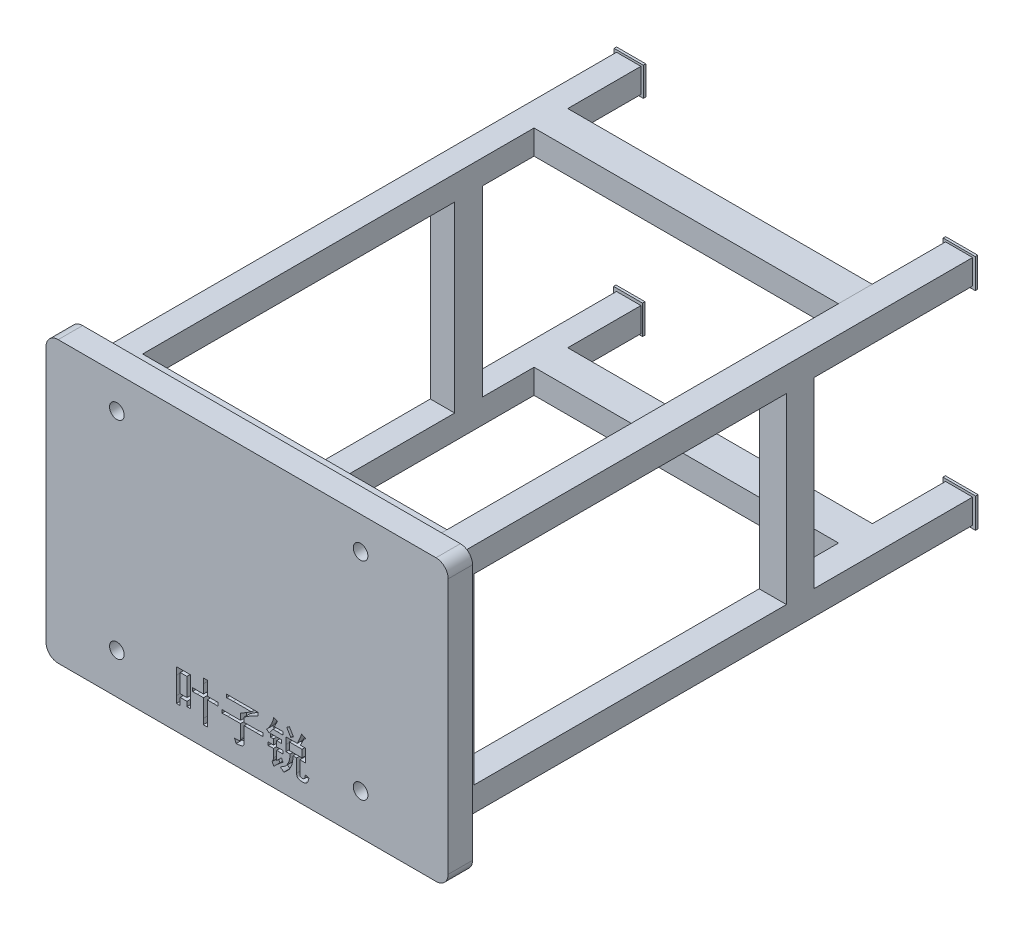
SolidWorks part; units mm, degrees
ref_plane "前视基准面" through (0, 0, 0) normal (0, 0, 1) x (1, 0, 0)
ref_plane "上视基准面" through (0, 0, 0) normal (0, 1, 0) x (1, 0, 0)
ref_plane "右视基准面" through (0, 0, 0) normal (1, 0, 0) x (0, 0, -1)
other "Configuration Table"
sketch "草图1" plane through (0, 0, 0) normal (0, 0, 1) x (1, 0, 0)
  line L0 (-38.1382, 236.709) -> (-38.1382, 26.709)
  line L1 (-28.1382, 16.709) -> (281.8618, 16.709)
  line L2 (291.8618, 26.709) -> (291.8618, 236.709)
  line L3 (281.8618, 246.709) -> (-28.1382, 246.709)
  arc A0 (281.8618, 16.709) -> (291.8618, 26.709) centre (281.8618, 26.709) ccw
  arc A1 (291.8618, 236.709) -> (281.8618, 246.709) centre (281.8618, 236.709) ccw
  arc A2 (-38.1382, 26.709) -> (-28.1382, 16.709) centre (-28.1382, 26.709) ccw
  arc A3 (-38.1382, 236.709) -> (-28.1382, 246.709) centre (-28.1382, 236.709) cw
  dimension "D1" = 10
extrude "凸台-拉伸1" add sketch "草图1" along normal blind 20
sketch "草图2" plane through (0, 0, 20) normal (0, 0, 1) x (1, 0, 0)
  circle A0 centre (20, 220) radius 6
  circle A1 centre (20, 50) radius 6
  circle A2 centre (220, 50) radius 6
  circle A3 centre (220, 220) radius 6
sketch "草图3" plane through (0, 0, 0) normal (0, 0, -1) x (-1, 0, 0)
  line L1 (-250, 230) -> (0, 230)
  line L2 (-250, 230) -> (-250, 210)
  line L3 (-250, 210) -> (0, 210)
  line L4 (0, 230) -> (0, 210)
extrude "凸台-拉伸2" add sketch "草图3" along normal blind 20
sketch "草图4" plane through (0, 0, 0) normal (0, 0, -1) x (-1, 0, 0)
  line L4 (-250, 60) -> (0, 60)
  line L5 (-250, 60) -> (-250, 40)
  line L6 (-250, 40) -> (0, 40)
  line L7 (0, 60) -> (0, 40)
extrude "凸台-拉伸3" add sketch "草图4" along normal blind 20
extrude "切除-拉伸2" cut sketch "草图2<3>" against normal blind 40
sketch "草图2<3>" plane through (0, 0, 20) normal (0, 0, 1) x (1, 0, 0) same geometry as "草图2"
sketch "草图5" plane through (0, 0, 0) normal (0, 0, -1) x (-1, 0, 0)
  line L1 (-272.2176, 230.2498) -> (-250, 230.2498)
  line L2 (-272.2176, 230.2498) -> (-272.2176, 210)
  line L3 (-272.2176, 210) -> (-250, 210)
  line L4 (-250, 230.2498) -> (-250, 210)
  line L8 (-250, 60) -> (-272.2176, 60)
  line L9 (-250, 60) -> (-250, 40)
  line L10 (-250, 40) -> (-272.2176, 40)
  line L11 (-272.2176, 60) -> (-272.2176, 40)
  line L12 (0, 230) -> (20, 230)
  line L13 (0, 230) -> (0, 210)
  line L14 (0, 210) -> (20, 210)
  line L15 (20, 230) -> (20, 210)
  line L17 (0, 60) -> (20, 60)
  line L18 (0, 60) -> (0, 40)
  line L19 (0, 40) -> (20, 40)
  line L20 (20, 60) -> (20, 40)
extrude "凸台-拉伸4" add sketch "草图5" along normal blind 430
sketch "草图6" plane through (0, 0, 0) normal (0, 0, -1) x (-1, 0, 0)
  line L0 (-272.2176, 210) -> (20, 210) construction
  line L1 (-272.2176, 210) -> (-250, 210)
  line L2 (-272.2176, 210) -> (-272.2176, 60)
  line L3 (-272.2176, 60) -> (-250, 60)
  line L4 (-250, 210) -> (-250, 60)
  line L5 (0, 210) -> (20, 210)
  line L6 (0, 210) -> (0, 60)
  line L7 (0, 60) -> (20, 60)
  line L8 (20, 210) -> (20, 60)
extrude "凸台-拉伸6" add sketch "草图6" along normal blind 20
extrude "凸台-拉伸13" add sketch "草图6<5>" along normal blind 300
sketch "草图6<5>" plane through (0, 0, 0) normal (0, 0, -1) x (-1, 0, 0) same geometry as "草图6"
sketch "草图10" plane through (272.2176, 0, 0) normal (1, 0, 0) x (0, 0, -1)
  line L3 (277.2157, 210) -> (20.8428, 210)
  line L4 (277.2157, 210) -> (277.2157, 60)
  line L5 (277.2157, 60) -> (20.8428, 60)
  line L6 (20.8428, 210) -> (20.8428, 60)
extrude "切除-拉伸9" cut sketch "草图10" against normal blind 400
extrude "凸台-拉伸14" add sketch "草图4<4>" along normal blind 370
sketch "草图4<4>" plane through (0, 0, 0) normal (0, 0, -1) x (-1, 0, 0) same geometry as "草图4"
extrude "凸台-拉伸15" add sketch "草图3<4>" along normal blind 370
sketch "草图3<4>" plane through (0, 0, 0) normal (0, 0, -1) x (-1, 0, 0) same geometry as "草图3"
sketch "草图11" plane through (0, 40, 0) normal (0, -1, 0) x (-1, 0, 0)
  line L3 (0, 342.3396) -> (-249.8503, 342.3396)
  line L4 (0, 342.3396) -> (0, 21.1415)
  line L5 (0, 21.1415) -> (-249.8503, 21.1415)
  line L6 (-249.8503, 342.3396) -> (-249.8503, 21.1415)
extrude "切除-拉伸10" cut sketch "草图11" against normal blind 400
extrude "切除-拉伸12" cut sketch "草图2" against normal blind 200
sketch "草图13" plane through (0, 0, -430) normal (0, 0, -1) x (-1, 0, 0)
  line L1 (-1.3669, 62.4139) -> (22.4226, 62.4139)
  line L2 (-1.3669, 62.4139) -> (-1.3669, 38.6245)
  line L3 (-1.3669, 38.6245) -> (22.4226, 38.6245)
  line L4 (22.4226, 62.4139) -> (22.4226, 38.6245)
extrude "凸台-拉伸17" add sketch "草图13" along normal blind 2
sketch "草图14" plane through (0, 0, -430) normal (0, 0, -1) x (-1, 0, 0)
  line L1 (-274.4001, 231.9958) -> (-247.9916, 231.9958)
  line L2 (-274.4001, 231.9958) -> (-274.4001, 207.7698)
  line L3 (-274.4001, 207.7698) -> (-247.9916, 207.7698)
  line L4 (-247.9916, 231.9958) -> (-247.9916, 207.7698)
extrude "凸台-拉伸18" add sketch "草图14" along normal blind 2
sketch "草图15" plane through (0, 0, -430) normal (0, 0, -1) x (-1, 0, 0)
  line L1 (-274.6184, 61.9774) -> (-247.7734, 61.9774)
  line L2 (-274.6184, 61.9774) -> (-274.6184, 37.5332)
  line L3 (-274.6184, 37.5332) -> (-247.7734, 37.5332)
  line L4 (-247.7734, 61.9774) -> (-247.7734, 37.5332)
extrude "凸台-拉伸19" add sketch "草图15" along normal blind 2
sketch "草图17" plane through (0, 0, -430) normal (0, 0, -1) x (-1, 0, 0)
  line L1 (-2.0216, 208.2063) -> (21.9861, 208.2063)
  line L2 (-2.0216, 208.2063) -> (-2.0216, 231.7775)
  line L3 (-2.0216, 231.7775) -> (21.9861, 231.7775)
  line L4 (21.9861, 208.2063) -> (21.9861, 231.7775)
extrude "凸台-拉伸21" add sketch "草图17" along normal blind 2
sketch "草图20" plane through (0, 0, 20) normal (0, 0, 1) x (1, 0, 0)
  text T0 "叶子锐" font "黑体" height 25
extrude "切除-拉伸13" cut sketch "草图20" against normal blind 5
